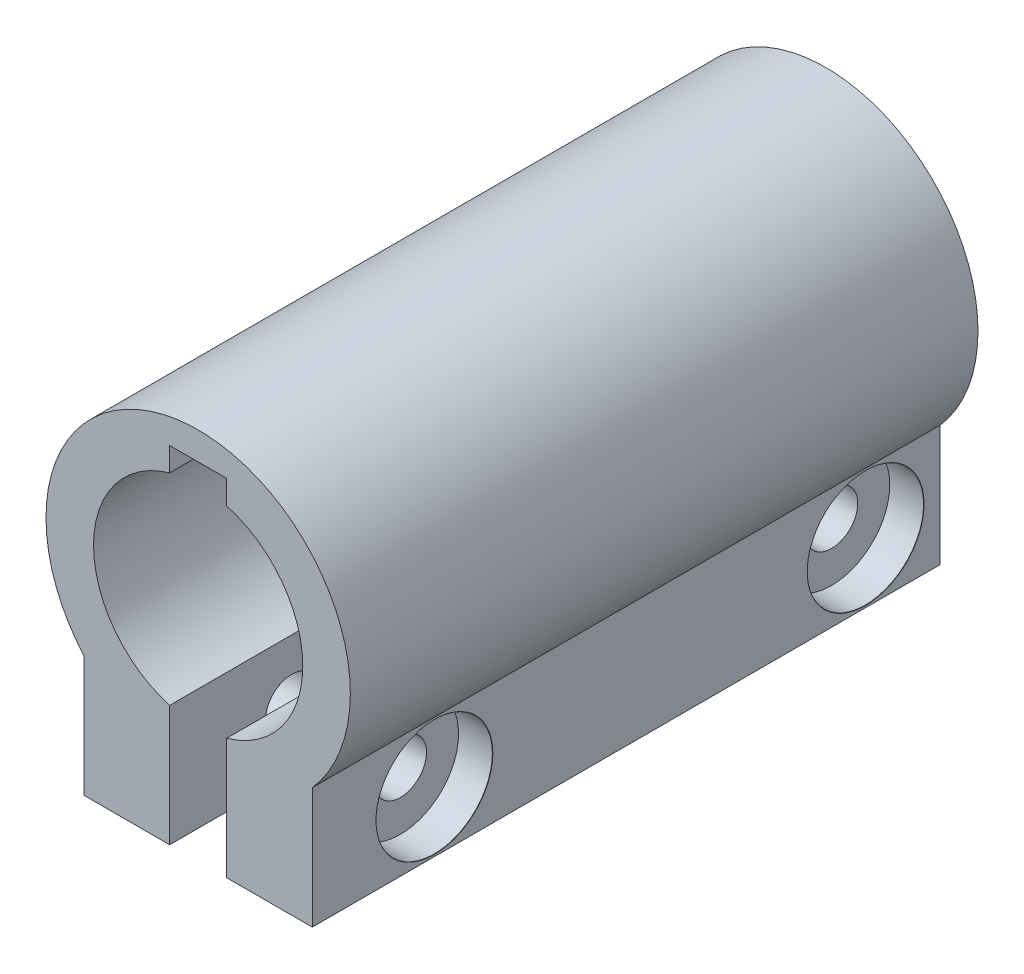
SolidWorks part; units mm, degrees
ref_plane "Front Plane" through (0, 0, 0) normal (0, 0, 1) x (1, 0, 0)
ref_plane "Top Plane" through (0, 0, 0) normal (0, 1, 0) x (1, 0, 0)
ref_plane "Right Plane" through (0, 0, 0) normal (1, 0, 0) x (0, 0, -1)
sketch "Sketch1" plane through (0, 0, 0) normal (0, 0, 1) x (1, 0, 0)
  circle A0 centre (0, 0) radius 11
  circle A1 centre (0, 0) radius 16
  dimension "D1" = 22
  dimension "D2" = 5
extrude "Boss-Extrude1" add sketch "Sketch1" along normal blind 33 and the other way blind 33
sketch "Sketch2" plane through (0, 0, 33) normal (0, 0, 1) x (1, 0, 0)
  line L0 (-3, 10.583) -> (-3, 13.083)
  line L2 (3, 13.083) -> (3, 10.583)
  line L3 (0, 0) -> (0, 13.083) construction
  line L4 (-3, 13.083) -> (0, 13.083)
  line L5 (0, 13.083) -> (3, 13.083)
  line L6 (-3, 10.583) -> (3, 10.583)
  circle A3 centre (0, 0) radius 11 construction
  dimension "D1" = 3
  dimension "D2" = 3
  dimension "D3" = 2.5
  dimension "D4" = 2.5
extrude "Cut-Extrude1" cut sketch "Sketch2" against normal blind 33
mirror "Mirror2" about plane through (0, 0, 0) normal (0, 0, -1) of "Cut-Extrude1"
sketch "Sketch3" plane through (0, 0, 33) normal (0, 0, 1) x (1, 0, 0)
  line L0 (-3, -10.583) -> (-3, -15.7162)
  line L1 (-3, -15.7162) -> (-3, -10.583)
  line L2 (3, -10.583) -> (3, -15.7162)
  line L3 (-3, -10.583) -> (3, -10.583)
  line L4 (-3, -15.7162) -> (-3, -23.283)
  line L5 (-3, -23.283) -> (-12, -23.283)
  line L6 (-12, -23.283) -> (-12, -10.583)
  line L7 (-12, -10.583) -> (-3, -10.583)
  line L8 (3, -15.7162) -> (3, -23.283)
  line L9 (3, -23.283) -> (12, -23.283)
  line L10 (12, -23.283) -> (12, -10.583)
  line L11 (12, -10.583) -> (3, -10.583)
  arc A0 (-3, 10.583) -> (3, 10.583) centre (0, 0) ccw construction
  circle A1 centre (0, 0) radius 16 construction
  point P12 (-3, -10.8896)
  point P19 (0, 0)
  point P20 (-3, -10.8474)
  circle M6 centre (0, 0) radius 16
  dimension "D1" = 12.7
extrude "Boss-Extrude2" add sketch "Sketch3" against normal through all contours L6 L5 L4 M6 | L9 L10 L8 M6 region at (-7.8946, -18.4352, 33) region at (7.8946, -18.4352, 33)
sketch "Sketch4" plane through (0, 0, 33) normal (0, 0, 1) x (1, 0, 0)
  line L0 (-3, -10.583) -> (-3, -16.2715)
  line L1 (-3, -10.583) -> (3, -10.583)
  line L2 (3, -10.583) -> (3, -15.7162)
  line L3 (-3, -15.7162) -> (-3, -23.283) construction
  line L4 (-3, -16.2715) -> (3, -16.2715)
  line L5 (3, -15.7162) -> (3, -23.283) construction
  line L6 (3, -16.2715) -> (3, -15.7162)
  arc A0 (-3, 10.583) -> (3, 10.583) centre (0, 0) ccw construction
extrude "Cut-Extrude4" cut sketch "Sketch4" against normal through all
sketch "Sketch8" plane through (12, 0, 0) normal (1, 0, 0) x (0, 0, -1)
  line L0 (-33, -16.933) -> (-20.1582, -16.933)
  line L1 (-33, -23.283) -> (-33, -10.583) construction
hole_wizard "CBORE for M5 Hex Head Bolt3" positions "Sketch9" profile "Sketch10" counterbore size "M5" standard "ANSI Metric" end condition through all
sketch "Sketch9" plane through (12, 0, 0) normal (1, 0, 0) x (0, 0, -1)
  point P0 (-20.1582, -16.933)
  point P3 (25.1833, -16.933)
sketch "Sketch10" plane through (12, -16.933, 20.1582) normal (0, 1, 0) x (0, 0, -1)
  line L0 (0, 0) -> (0, 28)
  line L1 (0, 28) -> (2.75, 28)
  line L3 (2.75, 28) -> (2.75, 3.58)
  line L4 (6.12, 3.58) -> (2.75, 3.58)
  line L5 (6.12, 3.58) -> (6.12, 0.025)
  line L6 (6.12, 0.025) -> (6.145, 0)
  line L7 (6.145, 0) -> (0, 0)
  line L8 (-6.12, 0.025) -> (-6.145, 0) construction
  line L11 (0, -6.35) -> (0, 107.95) construction
  dimension "Thru Hole Dia." = 5.5
  dimension "Thru Hole Depth" = 28
  dimension "C'Bore Dia." = 12.24
  dimension "C'Bore Depth" = 3.58
  dimension "Near C'Sink Dia." = 12.29
  dimension "Near C'Sink Angle" = 90
